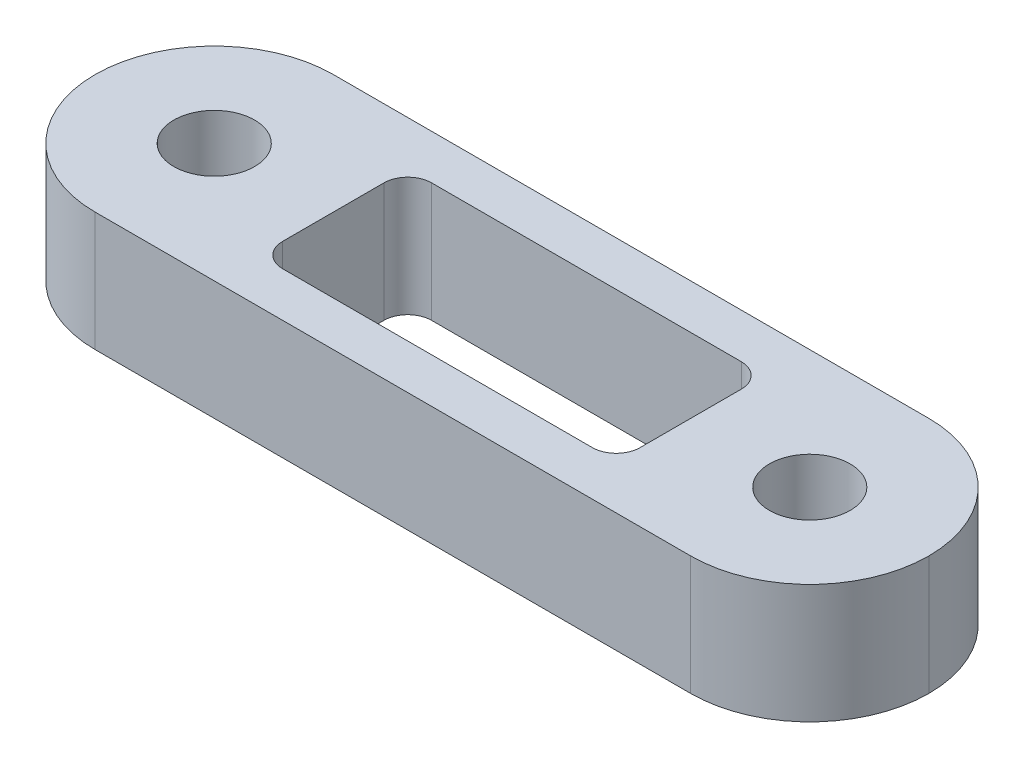
SolidWorks part; units mm, degrees
material "6061-T6 (SS)"
ref_plane "Front Plane" through (0, 0, 0) normal (0, 0, 1) x (1, 0, 0)
ref_plane "Top Plane" through (0, 0, 0) normal (0, 1, 0) x (1, 0, 0)
ref_plane "Right Plane" through (0, 0, 0) normal (1, 0, 0) x (0, 0, -1)
sketch "Sketch1" plane through (0, 0, 0) normal (0, 1, 0) x (1, 0, 0)
  line L0 (-15.875, 0) -> (0, 0) construction
  line L1 (-22.225, -6.35) -> (22.225, -6.35)
  line L2 (-22.225, -6.35) -> (-22.225, 6.35)
  line L3 (-22.225, 6.35) -> (22.225, 6.35)
  line L4 (22.225, -6.35) -> (22.225, 6.35)
  line L5 (-22.225, -6.35) -> (22.225, 6.35) construction
  line L6 (-22.225, 6.35) -> (22.225, -6.35) construction
  line L7 (0, 0) -> (15.875, 0) construction
  point P0 (0, 0)
  dimension "D1" = 44.45
  dimension "D2" = 12.7
  dimension "D4" = 31.75
extrude "Boss-Extrude4" add sketch "Sketch1" along normal blind 6.35
fillet "Fillet3" radius 6.35 4 edges at (22.225, 3.175, -6.35) (22.225, 3.175, 6.35) (-22.225, 3.175, -6.35) (-22.225, 3.175, 6.35)
sketch "Sketch7" plane through (0, 6.35, 0) normal (0, 1, 0) x (1, 0, 0)
  line L0 (-15.875, 0) -> (15.875, 0) construction
  point P4 (0, 0)
  dimension "D1" = 31.75
hole_wizard "#18 (0.1695) Diameter Hole2" positions "Sketch8" profile "Sketch9" hole size "#18" standard "ANSI Inch" end condition through all
sketch "Sketch8" plane through (0, 6.35, 0) normal (0, 1, 0) x (1, 0, 0)
  point P0 (-15.875, 0)
  point P3 (15.875, 0)
sketch "Sketch9" plane through (-15.875, 6.35, 0) normal (1, 0, 0) x (0, 0, 1)
  line L0 (0, 0) -> (0, 6.35)
  line L1 (0, 6.35) -> (2.1526, 6.35)
  line L2 (2.1526, 6.35) -> (2.1526, 0)
  line L5 (2.1526, 0) -> (0, 0)
  line L11 (0, -6.35) -> (0, 107.95) construction
  dimension "Thru Hole Dia." = 4.3053
  dimension "Thru Hole Depth" = 6.35
sketch "Sketch10" plane through (0, 6.35, 0) normal (0, 1, 0) x (1, 0, 0)
  line L1 (-8.255, 3.9688) -> (8.255, 3.9688)
  line L2 (-9.525, 2.6988) -> (-9.525, -2.6987)
  line L3 (-8.255, -3.9687) -> (8.255, -3.9687)
  line L4 (9.525, 2.6988) -> (9.525, -2.6987)
  line L5 (-9.525, 3.9688) -> (9.525, -3.9687) construction
  line L6 (-9.525, -3.9687) -> (9.525, 3.9688) construction
  arc A0 (-9.525, -2.6987) -> (-8.255, -3.9687) centre (-8.255, -2.6987) ccw
  arc A1 (8.255, -3.9687) -> (9.525, -2.6987) centre (8.255, -2.6987) ccw
  arc A2 (8.255, 3.9688) -> (9.525, 2.6988) centre (8.255, 2.6988) cw
  arc A3 (-8.255, 3.9688) -> (-9.525, 2.6988) centre (-8.255, 2.6988) ccw
  point P0 (0, 0)
  dimension "D1" = 1.27
  dimension "D2" = 19.05
  dimension "D3" = 7.9375
extrude "Cut-Extrude1" cut sketch "Sketch10" against normal blind 6.35
